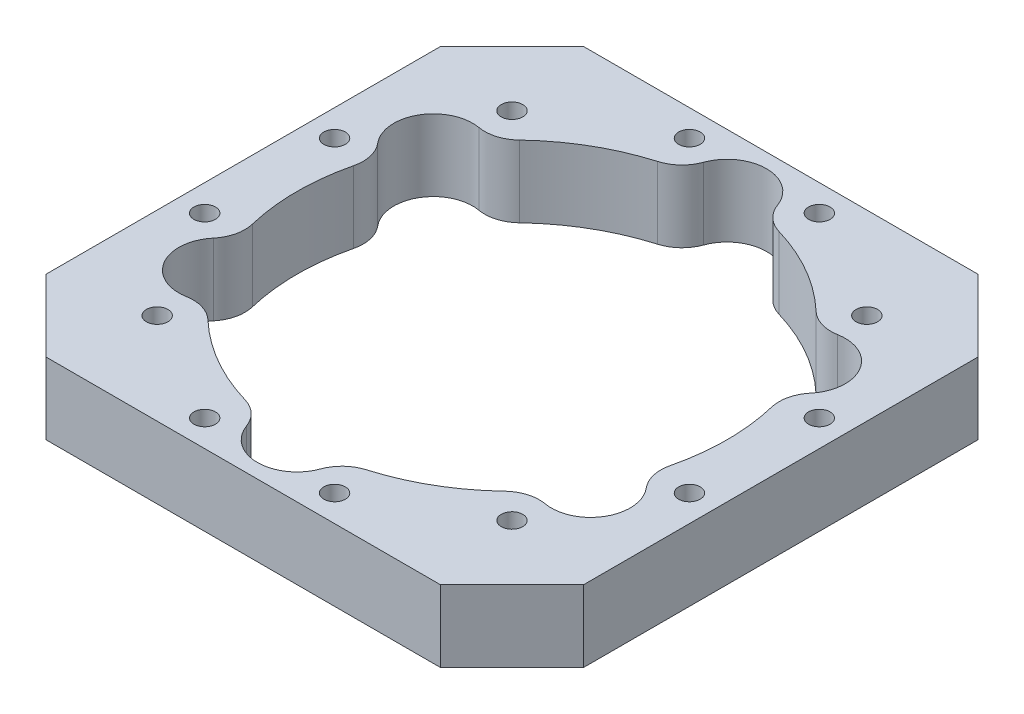
SolidWorks part; units mm, degrees
ref_plane "Front Plane" through (0, 0, 0) normal (0, 0, 1) x (1, 0, 0)
ref_plane "Top Plane" through (0, 0, 0) normal (0, 1, 0) x (1, 0, 0)
ref_plane "Right Plane" through (0, 0, 0) normal (1, 0, 0) x (0, 0, -1)
sketch "Sketch1" plane through (0, 0, 0) normal (0, 1, 0) x (1, 0, 0)
  line L0 (-49.1682, 0) -> (0, 0) construction
  line L1 (0, 0) -> (-48.4521, -12.9827) construction
  line L2 (-37.5, 37.5) -> (37.5, 37.5)
  line L3 (-37.5, 37.5) -> (-37.5, -37.5)
  line L4 (37.5, 37.5) -> (37.5, -37.5)
  line L5 (-37.5, -37.5) -> (37.5, -37.5)
  circle A0 centre (0, 0) radius 37.5 construction
  circle A1 centre (0, 0) radius 35 construction
  circle A2 centre (0, 0) radius 30
  circle A3 centre (0, 30) radius 5.5
  circle A4 centre (25.9808, 15) radius 5.5
  circle A5 centre (25.9808, -15) radius 5.5
  circle A6 centre (0, -30) radius 5.5
  circle A7 centre (-25.9808, -15) radius 5.5
  circle A8 centre (-25.9808, 15) radius 5.5
  circle A9 centre (-33.8074, -9.0587) radius 1.5
  circle A10 centre (-33.8074, 9.0587) radius 1.5
  circle A11 centre (-24.7487, 24.7487) radius 1.5
  circle A12 centre (-9.0587, 33.8074) radius 1.5
  circle A13 centre (9.0587, 33.8074) radius 1.5
  circle A14 centre (24.7487, 24.7487) radius 1.5
  circle A15 centre (33.8074, 9.0587) radius 1.5
  circle A16 centre (33.8074, -9.0587) radius 1.5
  circle A17 centre (24.7487, -24.7487) radius 1.5
  circle A18 centre (9.0587, -33.8074) radius 1.5
  circle A19 centre (-9.0587, -33.8074) radius 1.5
  circle A20 centre (-24.7487, -24.7487) radius 1.5
  point P19 (0, 0)
  point P47 (0, 0)
  dimension "D1" = 75
  dimension "D2" = 70
  dimension "D3" = 60
  dimension "D4" = 11
  dimension "D7" = 3
  dimension "D6" = 15
  dimension "D5" = 6
  dimension "D8" = 12
extrude "Boss-Extrude1" add sketch "Sketch1" along normal blind 10 contours A0 A20 A19 A18 A17 A16 A15 A14 A13 A12 A11 A10 A9 A8 A2 A3 A4 A5 A6 A7 region at (0, 0, -36.4393)
fillet "Fillet1" radius 5 12 edges at (5.4768, 5, -29.4958) (22.8057, 5, -19.491) (28.2826, 5, 10.0048) (28.2826, 5, -10.0048) (22.8057, 5, 19.491) (5.4768, 5, 29.4958) (-5.4768, 5, 29.4958) (-22.8057, 5, 19.491) (-28.2826, 5, 10.0048) (-28.2826, 5, -10.0048) (-22.8057, 5, -19.491) (-5.4768, 5, -29.4958)
chamfer "Chamfer1" distance 10 angle 45 4 edges at (-37.5, 5, 37.5) (37.5, 5, 37.5) (37.5, 5, -37.5) (-37.5, 5, -37.5)
